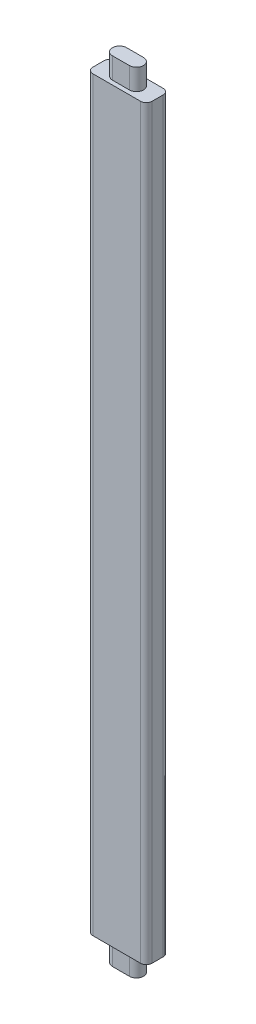
SolidWorks part; units mm, degrees
ref_plane "Front" through (0, 0, 0) normal (0, 0, 1) x (1, 0, 0)
ref_plane "Top" through (0, 0, 0) normal (0, 1, 0) x (1, 0, 0)
ref_plane "Right" through (0, 0, 0) normal (1, 0, 0) x (0, 0, -1)
sketch "Esquisse1" plane through (0, 0, 0) normal (0, 1, 0) x (1, 0, 0)
  line L1 (0, 0) -> (42, 0)
  line L2 (0, 0) -> (0, 16)
  line L3 (0, 16) -> (42, 16)
  line L4 (42, 0) -> (42, 16)
  dimension "D1" = 42
  dimension "D2" = 16
extrude "Boss.-Extru.1" add sketch "Esquisse1" along normal blind 530
sketch "Esquisse2" plane through (0, 530, 0) normal (0, 1, 0) x (1, 0, 0)
  line L0 (42, 8) -> (0, 8) construction
  line L1 (42, 0) -> (42, 16) construction
  line L2 (0, 16) -> (0, 0) construction
  line L3 (15, 8) -> (27, 8) construction
  line L4 (15, 13) -> (27, 13)
  line L5 (15, 3) -> (27, 3)
  arc A0 (15, 13) -> (15, 3) centre (15, 8) ccw
  arc A1 (27, 3) -> (27, 13) centre (27, 8) ccw
  point P8 (21, 8)
  dimension "D1" = 10
  dimension "D2" = 12
extrude "Boss.-Extru.2" add sketch "Esquisse2" along normal blind 15
extrude "Boss.-Extru.3" add sketch "Esquisse2<2>" against normal blind 15 from vertex starting at point (42, 0, 0)
sketch "Esquisse2<2>" plane through (0, 530, 0) normal (0, 1, 0) x (1, 0, 0) same geometry as "Esquisse2"
fillet "Congé1" radius 4 4 edges at (42, 265, 0) (42, 265, -16) (0, 265, -16) (0, 265, 0)
